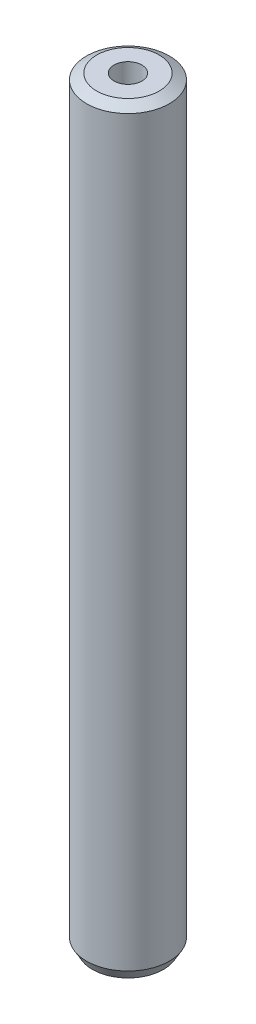
SolidWorks part; units mm, degrees
ref_plane "Front Plane" through (0, 0, 0) normal (0, 0, 1) x (1, 0, 0)
ref_plane "Top Plane" through (0, 0, 0) normal (0, 1, 0) x (1, 0, 0)
ref_plane "Right Plane" through (0, 0, 0) normal (1, 0, 0) x (0, 0, -1)
sketch "Sketch1" plane through (0, 0, 0) normal (0, 1, 0) x (1, 0, 0)
  circle A0 centre (0, 0) radius 22.5
  dimension "SHAFT_OD" = 45
extrude "Boss-Extrude1" add sketch "Sketch1" along normal blind 412.221
sketch "Sketch2" plane through (0, 0, 0) normal (0, 1, 0) x (1, 0, 0)
  circle A0 centre (0, 0) radius 7.5668
  dimension "BORE_D" = 15.1336
extrude "Cut-Extrude1" cut sketch "Sketch2" along normal through all
chamfer "Chamfer1" distance 3.1912 angle 60 2 edges at (0, 412.221, 22.5) (0, 0, 22.5) first distance on face at (0, 412.221, 22.5) first distance on face at (0, 0, 7.5668)
